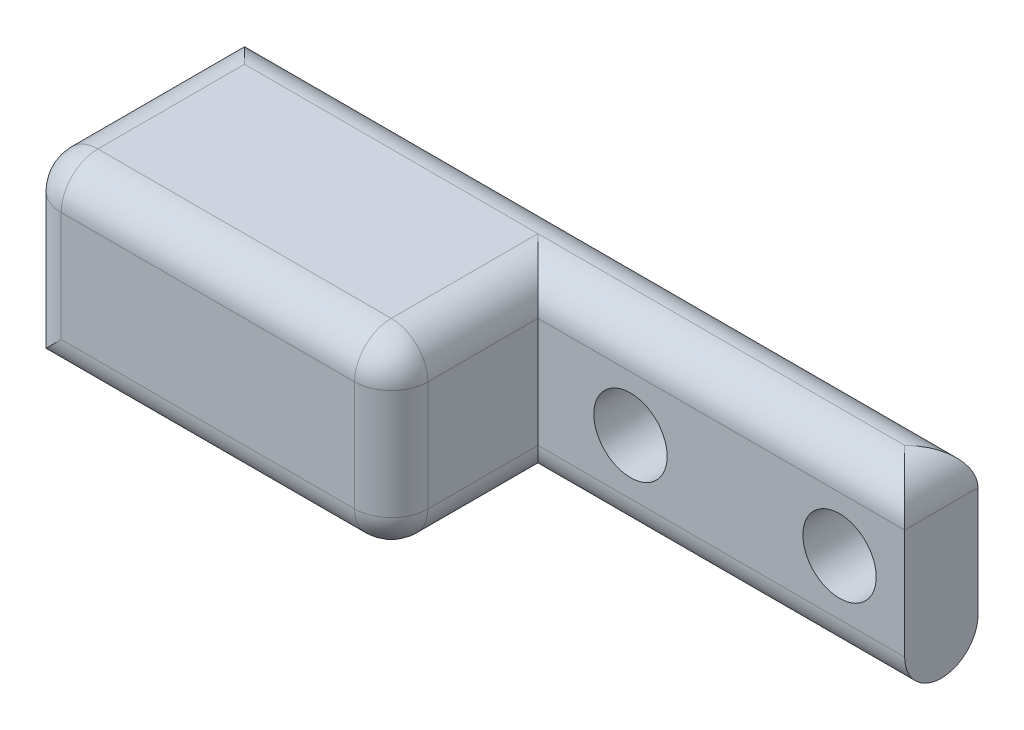
SolidWorks part; units mm, degrees
ref_plane "Front Plane" through (0, 0, 0) normal (0, 0, 1) x (1, 0, 0)
ref_plane "Top Plane" through (0, 0, 0) normal (0, 1, 0) x (1, 0, 0)
ref_plane "Right Plane" through (0, 0, 0) normal (1, 0, 0) x (0, 0, -1)
sketch "Sketch1" plane through (0, 0, 0) normal (0, 1, 0) x (1, 0, 0)
  line L0 (0, 0) -> (0, 6)
  line L1 (0, 6) -> (16.6085, 6)
  line L2 (10, 4) -> (10, 0)
  line L3 (10, 0) -> (0, 0)
  line L4 (10, 4) -> (20, 4)
  line L5 (16.6085, 6) -> (20, 6)
  line L6 (20, 6) -> (20, 4)
  dimension "D1" = 6
  dimension "D2" = 2
  dimension "D3" = 10
  dimension "D4" = 10
extrude "Boss-Extrude1" add sketch "Sketch1" along normal blind 5
sketch "Sketch2" plane through (0, 0, -4) normal (0, 0, 1) x (1, 0, 0)
  line L0 (10, 5) -> (20, 5) construction
  circle A0 centre (12.524, 2.5) radius 1
  circle A1 centre (18.224, 2.5) radius 1
  dimension "D1" = 2.5
  dimension "D2" = 5.7
extrude "Cut-Extrude1" cut sketch "Sketch2" against normal blind 5
fillet "Fillet1" radius 1 12 edges at (5, 0, 0) (5, 5, 0) (0, 5, -3) (10, 5, -6) (20, 5, -5) (15, 5, -4) (10, 5, -2) (0, 2.5, 0) (10, 2.5, 0) (10, 0, -2) (10, 0, -6) (15, 0, -4)
